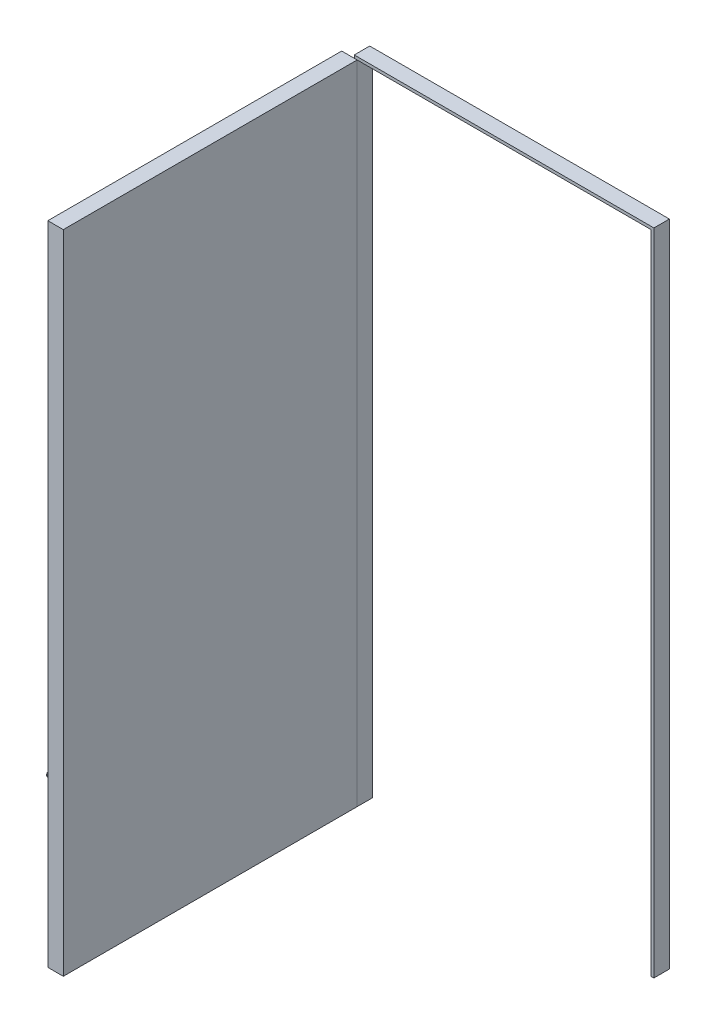
SolidWorks part; units mm, degrees
ref_plane "Front" through (0, 0, 0) normal (0, 0, 1) x (1, 0, 0)
ref_plane "Top" through (0, 0, 0) normal (0, 1, 0) x (1, 0, 0)
ref_plane "Right" through (0, 0, 0) normal (1, 0, 0) x (0, 0, -1)
sketch "Sketch1" plane through (0, 0, 0) normal (0, 0, 1) x (1, 0, 0)
  line L0 (965.2, 2114.55) -> (965.2, -2133.6)
  line L1 (-984.25, 2133.6) -> (984.25, 2133.6)
  line L2 (-984.25, 2133.6) -> (-984.25, -2133.6)
  line L3 (-984.25, -2133.6) -> (984.25, -2133.6) construction
  line L4 (984.25, 2133.6) -> (984.25, -2133.6)
  line L5 (-984.25, 2133.6) -> (984.25, -2133.6) construction
  line L6 (-984.25, -2133.6) -> (984.25, 2133.6) construction
  line L7 (-965.2, 2114.55) -> (965.2, 2114.55)
  line L8 (-965.2, 2114.55) -> (-965.2, -2133.6)
  line L9 (-984.25, -2133.6) -> (-965.2, -2133.6)
  line L10 (965.2, -2133.6) -> (984.25, -2133.6)
  point P0 (0, 0)
  dimension "D1" = 4267.2
  dimension "D3" = 1930.4
  dimension "D2" = 19.05
extrude "Boss-Extrude1" add sketch "Sketch1" along normal blind 101.6
sketch "Sketch2" plane through (0, -2133.6, 0) normal (0, -1, 0) x (1, 0, 0)
  line L0 (-965.2, 101.6) -> (-965.2, 2032)
  line L1 (-965.2, 2032) -> (-1066.8, 2032)
  line L2 (-1066.8, 2032) -> (-1066.8, 101.6)
  line L3 (-1066.8, 101.6) -> (-965.2, 101.6)
  line L4 (-965.2, 0) -> (965.2, 0) construction
  dimension "D1" = 101.6
  dimension "D2" = 90
extrude "Boss-Extrude2" add sketch "Sketch2" against normal up to surface (4248.15 mm away) separate body up to face at (0, 2114.55, 50.8)
sketch "Sketch3" plane through (0, 0, 2032) normal (0, 0, 1) x (1, 0, 0)
  line L0 (-1066.8, 2114.55) -> (-1066.8, -2133.6) construction
  line L1 (-1066.8, -736.6) -> (-1193.8, -736.6)
  line L2 (-1066.8, -736.6) -> (-1066.8, -787.4)
  line L3 (-1066.8, -1117.6) -> (-1193.8, -1117.6)
  line L4 (-1193.8, -736.6) -> (-1193.8, -1117.6)
  line L5 (-1066.8, -1066.8) -> (-1066.8, -1117.6)
  line L6 (-1066.8, -787.4) -> (-1143, -787.4)
  line L8 (-1066.8, -1066.8) -> (-1143, -1066.8)
  line L9 (-1143, -787.4) -> (-1143, -1066.8)
  line L10 (-1143, -787.4) -> (-1193.8, -787.4) construction
  line L11 (-1143, -787.4) -> (-1143, -736.6) construction
  line L12 (-1143, -1066.8) -> (-1143, -1117.6) construction
  line L13 (-965.2, -2133.6) -> (-1066.8, -2133.6) construction
  line L15 (-1066.8, -1219.2) -> (-1104.9, -1219.2)
  line L16 (-1066.8, -1219.2) -> (-1066.8, -1257.3)
  line L17 (-1066.8, -1257.3) -> (-1104.9, -1257.3)
  line L18 (-1104.9, -1219.2) -> (-1104.9, -1257.3)
  dimension "D1" = 50.8
  dimension "D2" = 1016
  dimension "D3" = 76.2
  dimension "D4" = 381
  dimension "D5" = 101.6
  dimension "D6" = 38.1
extrude "Boss-Extrude3" add sketch "Sketch3" along normal blind 38.1 from offset 228.6 offset against normal yes
fillet "Fillet1" radius 38.1 2 edges at (-1193.8, -1117.6, 1822.45) (-1193.8, -736.6, 1822.45)
fillet "Fillet2" radius 12.7 2 edges at (-1143, -1066.8, 1822.45) (-1143, -787.4, 1822.45)
fillet "Fillet3" radius 12.7 20 edges at (-1098.55, -1066.8, 1803.4) (-1139.2803, -1063.0803, 1803.4) (-1143, -927.1, 1803.4) (-1139.2803, -791.1197, 1803.4) (-1098.55, -787.4, 1803.4) (-1111.25, -736.6, 1803.4) (-1182.6408, -747.7592, 1803.4) (-1193.8, -927.1, 1803.4) (-1182.6408, -1106.4408, 1803.4) (-1111.25, -1117.6, 1803.4) (-1182.6408, -747.7592, 1841.5) (-1111.25, -736.6, 1841.5) (-1098.55, -787.4, 1841.5) (-1139.2803, -791.1197, 1841.5) (-1143, -927.1, 1841.5) (-1139.2803, -1063.0803, 1841.5) (-1098.55, -1066.8, 1841.5) (-1111.25, -1117.6, 1841.5) (-1182.6408, -1106.4408, 1841.5) (-1193.8, -927.1, 1841.5)
fillet "Fillet4" radius 19.05 4 edges at (-1085.85, -1257.3, 1803.4) (-1085.85, -1219.2, 1803.4) (-1085.85, -1257.3, 1841.5) (-1085.85, -1219.2, 1841.5)
sketch "Sketch4" plane through (-1104.9, 0, 0) normal (-1, 0, 0) x (0, 0, 1)
  line L0 (1822.45, -1219.2) -> (1822.45, -1257.3) construction
  circle A0 centre (1822.45, -1238.25) radius 9.525
  dimension "D1" = 19.05
extrude "Boss-Extrude4" add sketch "Sketch4" along normal blind 152.4
sketch "Sketch5" plane through (-1257.3, 0, 0) normal (-1, 0, 0) x (0, 0, 1)
  line L0 (1803.4, -1238.25) -> (1841.5, -1238.25)
  circle A0 centre (1822.45, -1238.25) radius 19.05 construction
  arc A1 (1803.4, -1238.25) -> (1841.5, -1238.25) centre (1822.45, -1238.25) cw
  dimension "D1" = 38.1
revolve "Revolve1" add sketch "Sketch5" angle 360 about L0
